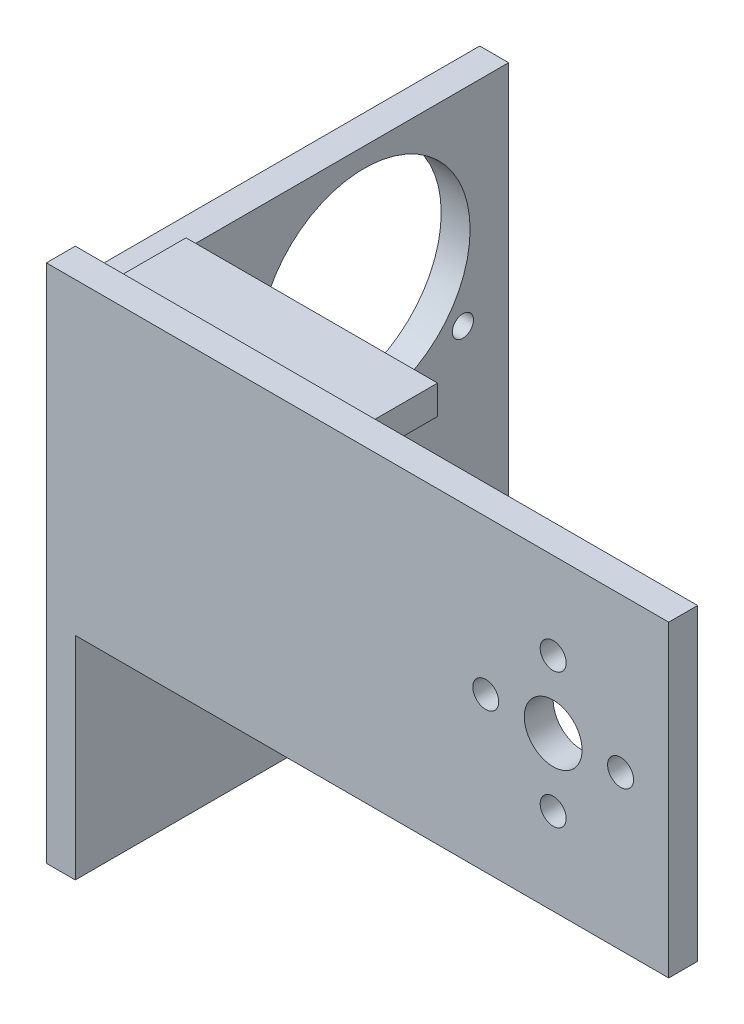
SolidWorks part; units mm, degrees
ref_plane "Front Plane" through (0, 0, 0) normal (0, 0, 1) x (1, 0, 0)
ref_plane "Top Plane" through (0, 0, 0) normal (0, 1, 0) x (1, 0, 0)
ref_plane "Right Plane" through (0, 0, 0) normal (1, 0, 0) x (0, 0, -1)
ref_plane "PZ_p27_000" through (0, 0, 27) normal (0, 0, 1) x (1, 0, 0)
sketch "S_box1" plane through (0, 0, 27) normal (0, 0, 1) x (1, 0, 0)
  line L0 (-52.625, -16) -> (12, -16)
  line L1 (12, -16) -> (12, 16)
  line L2 (12, 16) -> (-52.625, 16)
  line L3 (-52.625, 16) -> (-52.625, -16)
  dimension "P1" = 52.625
  dimension "P2" = 16
  dimension "P3" = 12
  dimension "P4" = 16
  dimension "P5" = 12
  dimension "P6" = 16
  dimension "P7" = 52.625
  dimension "P8" = 16
extrude "Boss_1" add sketch "S_box1" along normal blind 3
ref_plane "PZ_m15_000" through (0, 0, -15) normal (0, 0, 1) x (1, 0, 0)
sketch "S_box2" plane through (0, 0, -15) normal (0, 0, 1) x (1, 0, 0)
  line L0 (-52.625, -38) -> (-49.625, -38)
  line L1 (-49.625, -38) -> (-49.625, 13)
  line L2 (-49.625, 13) -> (-52.625, 13)
  line L3 (-52.625, 13) -> (-52.625, -38)
  dimension "P1" = 52.625
  dimension "P2" = 38
  dimension "P3" = 49.625
  dimension "P4" = 38
  dimension "P5" = 49.625
  dimension "P6" = 13
  dimension "P7" = 52.625
  dimension "P8" = 13
extrude "Boss_2" add sketch "S_box2" along normal blind 45
ref_plane "PZ_p18_000" through (0, 0, 18) normal (0, 0, 1) x (1, 0, 0)
sketch "S_box3" plane through (0, 0, 18) normal (0, 0, 1) x (1, 0, 0)
  line L0 (-50.125, 10.5) -> (-24, 10.5)
  line L1 (-24, 10.5) -> (-24, 13.5)
  line L2 (-24, 13.5) -> (-50.125, 13.5)
  line L3 (-50.125, 13.5) -> (-50.125, 10.5)
  dimension "P1" = 50.125
  dimension "P2" = 10.5
  dimension "P3" = 24
  dimension "P4" = 10.5
  dimension "P5" = 24
  dimension "P6" = 13.5
  dimension "P7" = 50.125
  dimension "P8" = 13.5
extrude "Boss_3" add sketch "S_box3" along normal blind 11.5
sketch "S_box4" plane through (0, 0, 18) normal (0, 0, 1) x (1, 0, 0)
  line L0 (-50.125, -16) -> (-24, -16)
  line L1 (-24, -16) -> (-24, -13)
  line L2 (-24, -13) -> (-50.125, -13)
  line L3 (-50.125, -13) -> (-50.125, -16)
  dimension "P1" = 50.125
  dimension "P2" = 16
  dimension "P3" = 24
  dimension "P4" = 16
  dimension "P5" = 24
  dimension "P6" = 13
  dimension "P7" = 50.125
  dimension "P8" = 13
extrude "Boss_4" add sketch "S_box4" along normal blind 11.5
ref_plane "PZ_p26_900" through (0, 0, 26.9) normal (0, 0, 1) x (1, 0, 0)
sketch "S_hole5" plane through (0, 0, 26.9) normal (0, 0, 1) x (1, 0, 0)
  circle A0 centre (0, 0) radius 3
  dimension "D1_S_hole5" = 6
extrude "Hole_5" cut sketch "S_hole5" along normal blind 3.2
sketch "S_hole6" plane through (0, 0, 26.9) normal (0, 0, 1) x (1, 0, 0)
  circle A0 centre (7, 0) radius 1.35
  dimension "D1_S_hole6" = 2.7
  dimension "P2" = 7
extrude "Hole_6" cut sketch "S_hole6" along normal blind 3.2
sketch "S_hole7" plane through (0, 0, 26.9) normal (0, 0, 1) x (1, 0, 0)
  circle A0 centre (0, 7) radius 1.35
  dimension "D1_S_hole7" = 2.7
  dimension "P2" = 7
extrude "Hole_7" cut sketch "S_hole7" along normal blind 3.2
sketch "S_hole8" plane through (0, 0, 26.9) normal (0, 0, 1) x (1, 0, 0)
  circle A0 centre (-7, 0) radius 1.35
  dimension "D1_S_hole8" = 2.7
  dimension "P2" = 7
extrude "Hole_8" cut sketch "S_hole8" along normal blind 3.2
sketch "S_hole9" plane through (0, 0, 26.9) normal (0, 0, 1) x (1, 0, 0)
  circle A0 centre (0, -7) radius 1.35
  dimension "D1_S_hole9" = 2.7
  dimension "P2" = 7
extrude "Hole_9" cut sketch "S_hole9" along normal blind 3.2
ref_plane "PX_m52_725" through (-52.725, 0, 0) normal (1, 0, 0) x (0, 0, -1)
sketch "S_hole10" plane through (-52.725, 0, 0) normal (1, 0, 0) x (0, 0, -1)
  circle A0 centre (0, 0) radius 11
  dimension "D1_S_hole10" = 22
extrude "Hole_10" cut sketch "S_hole10" along normal blind 3.2
sketch "S_hole11" plane through (-52.725, 0, 0) normal (1, 0, 0) x (0, 0, -1)
  circle A0 centre (10.25, -8.3) radius 1.1
  dimension "D1_S_hole11" = 2.2
  dimension "P2" = 10.25
  dimension "P3" = 8.3
extrude "Hole_11" cut sketch "S_hole11" along normal blind 3.2
sketch "S_hole12" plane through (-52.725, 0, 0) normal (1, 0, 0) x (0, 0, -1)
  circle A0 centre (-10.25, -8.3) radius 1.1
  dimension "D1_S_hole12" = 2.2
  dimension "P2" = 10.25
  dimension "P3" = 8.3
extrude "Hole_12" cut sketch "S_hole12" along normal blind 3.2
sketch "S_hole13" plane through (-52.725, 0, 0) normal (1, 0, 0) x (0, 0, -1)
  circle A0 centre (10.25, -32.75) radius 1.1
  dimension "D1_S_hole13" = 2.2
  dimension "P2" = 10.25
  dimension "P3" = 32.75
extrude "Hole_13" cut sketch "S_hole13" along normal blind 3.2
sketch "S_hole14" plane through (-52.725, 0, 0) normal (1, 0, 0) x (0, 0, -1)
  circle A0 centre (-10.25, -32.75) radius 1.1
  dimension "D1_S_hole14" = 2.2
  dimension "P2" = 10.25
  dimension "P3" = 32.75
extrude "Hole_14" cut sketch "S_hole14" along normal blind 3.2
equation "\"plate_t\" = 3"
equation "\"clearance\" = 0.4"
